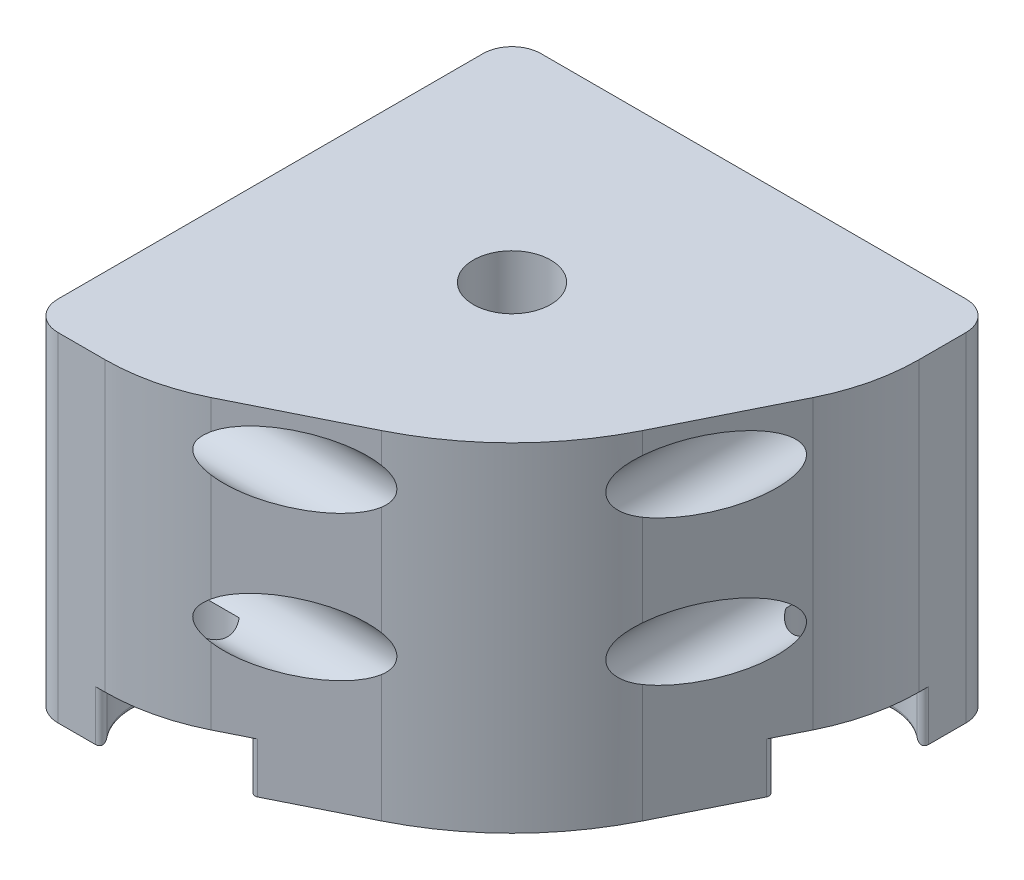
SolidWorks part; units mm, degrees
ref_plane "Plan de face" through (0, 0, 0) normal (0, 0, 1) x (1, 0, 0)
ref_plane "Plan de dessus" through (0, 0, 0) normal (0, 1, 0) x (1, 0, 0)
ref_plane "Plan de droite" through (0, 0, 0) normal (1, 0, 0) x (0, 0, -1)
sketch "Esquisse1" plane through (0, 0, 0) normal (0, 1, 0) x (1, 0, 0)
  line L0 (25, 25) -> (25, 30.1654) construction
  line L1 (-25, -25) -> (0.1127, -25)
  line L2 (-25, -25) -> (-25, 25)
  line L3 (-25, 25) -> (25, 25)
  line L4 (25, -0.1127) -> (25, 25)
  line L5 (-25, -25) -> (25, 25) construction
  line L6 (-25, 25) -> (25, -25) construction
  line L7 (25, 30.1654) -> (15, 30.1654) construction
  line L8 (15, 30.1654) -> (15, 25) construction
  line L9 (-25, -25) -> (-31.9159, -25) construction
  line L10 (-31.9159, -25) -> (-31.9159, -15) construction
  line L11 (-31.9159, -15) -> (-25, -15) construction
  line L12 (-25, -15) -> (25, -15) construction
  line L13 (15, 25) -> (15, -25) construction
  line L14 (0.1127, -25) -> (25, -0.1127) construction
  line L15 (25, -0.1127) -> (25, -25) construction
  line L16 (0.1127, -25) -> (25, -25) construction
  line L17 (-12.4437, -25) -> (-12.4437, -12.4437) construction
  line L18 (25, 12.4437) -> (12.4437, 12.4437) construction
  line L19 (12.5563, -12.5563) -> (-12.4437, -25)
  line L20 (12.5563, -12.5563) -> (25, 12.4437)
  circle A0 centre (-3, 3) radius 16 construction
  circle A1 centre (-3, 3) radius 4
  circle A2 centre (-12.4437, -20) radius 6.5 construction
  circle A3 centre (-12.4437, -20) radius 3 construction
  circle A4 centre (20, 12.4437) radius 3 construction
  circle A5 centre (20, 12.4437) radius 6.5 construction
  point P0 (0, 0)
  dimension "D2" = 32
  dimension "D4" = 8
  dimension "D5" = 22
  dimension "D6" = 13
  dimension "D7" = 6
  dimension "D1" = 50
  dimension "D3" = 22
  dimension "D8" = 5
  dimension "D9" = 12.5563
extrude "Boss.-Extru.1" add sketch "Esquisse1" along normal blind 35 contours L19 L20 L4 L3 L2 L1 A1 A3 A4 region at (-24.2929, 0, 0)
sketch "Esquisse16" plane through (0, 0, 0) normal (0, -1, 0) x (1, 0, 0)
  line L0 (-25, -25) -> (12.5563, 12.5563) construction
  line L1 (-25, 25) -> (25, -25) construction
  line L2 (-12.4437, 25) -> (-12.4437, 12.4437) construction
  line L3 (25, -12.4437) -> (12.4437, -12.4437) construction
  line L4 (-25, 25) -> (-12.4437, 25) construction
  circle A0 centre (-12.4437, 20) radius 3
  circle A1 centre (20, -12.4437) radius 3
  dimension "D1" = 6
  dimension "D2" = 6
  dimension "D3" = 5
  dimension "D4" = 5
  dimension "D5" = 90
extrude "Enlèv. mat.-Extru.8" cut sketch "Esquisse16" against normal blind 12
sketch "Esquisse2" plane through (0, 0, 0) normal (0, 1, 0) x (1, 0, 0)
  circle A0 centre (-3, 3) radius 16
  dimension "D1" = 32
extrude "Enlèv. mat.-Extru.1" cut sketch "Esquisse2" along normal blind 19
sketch "Esquisse4" plane through (-25, 0, 0) normal (-1, 0, 0) x (0, 0, 1)
  line L0 (20, 31.5) -> (20, 13.5) construction
  line L3 (25, 35) -> (25, 0) construction
  line L4 (25, 35) -> (-25, 35) construction
  line L5 (25, 0) -> (-25, 0) construction
  circle A0 centre (20, 30) radius 1.5
  circle A1 centre (20, 15) radius 1.5
  dimension "D2" = 3
  dimension "D1" = 5
  dimension "D3" = 5
  dimension "D4" = 15
extrude "Enlèv. mat.-Extru.2" cut sketch "Esquisse4" against normal up to surface (19.588 mm away) up to face at (0.0563, 17.5, 18.7782)
sketch "Esquisse5" plane through (0, 0, -25) normal (0, 0, -1) x (-1, 0, 0)
  line L0 (-19.1868, 31.5) -> (-19.1868, 13.5) construction
  line L1 (25, 35) -> (-25, 35) construction
  line L2 (25, 0) -> (-25, 0) construction
  circle A0 centre (-19.1868, 30) radius 1.5
  circle A1 centre (-19.1868, 15) radius 1.5
  dimension "D3" = 3
  dimension "D1" = 5
  dimension "D2" = 15
extrude "Enlèv. mat.-Extru.3" cut sketch "Esquisse5" against normal up to surface (27.2489 mm away) up to face at (18.7782, 17.5, 0.0563)
sketch "Esquisse15" plane through (0, 0, 0) normal (0, -1, 0) x (1, 0, 0)
  circle A2 centre (-12.4437, 20) radius 6.75
  circle A3 centre (20, -12.4437) radius 6.75
  dimension "D1" = 13.5
  dimension "D2" = 13.5
extrude "Enlèv. mat.-Extru.7" cut sketch "Esquisse15" against normal blind 5.2
sketch3d "Esquisse3D3" plane through (0, 0, 0) normal (0, 0, 1) x (1, 0, 0)
  dimension "D1" = 90
sketch "Esquisse11" plane through (-19, 0, 0) normal (1, 0, 0) x (0, 0, -1)
  circle A0 centre (-20, 30) radius 3.5
  circle A1 centre (-20, 15) radius 3.5
  dimension "D1" = 7
  dimension "D2" = 7
extrude "Enlèv. mat.-Extru.5" cut sketch "Esquisse11" along normal up to next
sketch "Esquisse13" plane through (0, 35, 0) normal (0, 1, 0) x (1, 0, 0)
  line L0 (25, 19) -> (-25, 19) construction
  line L1 (25, 12.4437) -> (25, 25) construction
  line L2 (-25, -25) -> (-25, 25) construction
  line L3 (-25, 25) -> (25, 25) construction
  dimension "D1" = 6
sketch3d "Esquisse3D5" plane through (0, 0, 0) normal (0, 0, 1) x (1, 0, 0)
  dimension "D1" = 90
sketch "Esquisse14" plane through (0, 0, -19) normal (0, 0, -1) x (-1, 0, 0)
  circle A0 centre (-19.1868, 30) radius 3.5
  circle A1 centre (-19.1868, 15) radius 3.5
  dimension "D1" = 7
  dimension "D2" = 7
extrude "Enlèv. mat.-Extru.6" cut sketch "Esquisse14" against normal up to next
fillet "Congé 1 2mm" radius 2 2 edges at (-3, 0, 13) (-3, 19, 13)
fillet "Congé 2 7mm" radius 7 1 edges at (-3, 19, 1)
fillet "Congé 4 30mm" radius 30 1 edges at (12.5563, 17.5, 12.5563)
fillet "Congé 5 20mm" radius 20 2 edges at (25, 20.1, -12.4437) (-12.4437, 20.1, 25)
fillet "Congé 6 3mm" radius 3 3 edges at (25, 17.5, -25) (-25, 17.5, -25) (-25, 17.5, 25)
fillet "Congé 8 0.5mm" radius 0.5 10 edges at (-25, 15, 21.5) (-25, 30, 21.5) (17.6868, 15, -25) (17.6868, 30, -25) (-14.3443, 0, 13.5231) (13.5231, 0, -14.3443) (24.9993, 2.6, -16.979) (21.7559, 2.6, -5.926) (-5.926, 2.6, 21.7559) (-16.979, 2.6, 24.9993)
